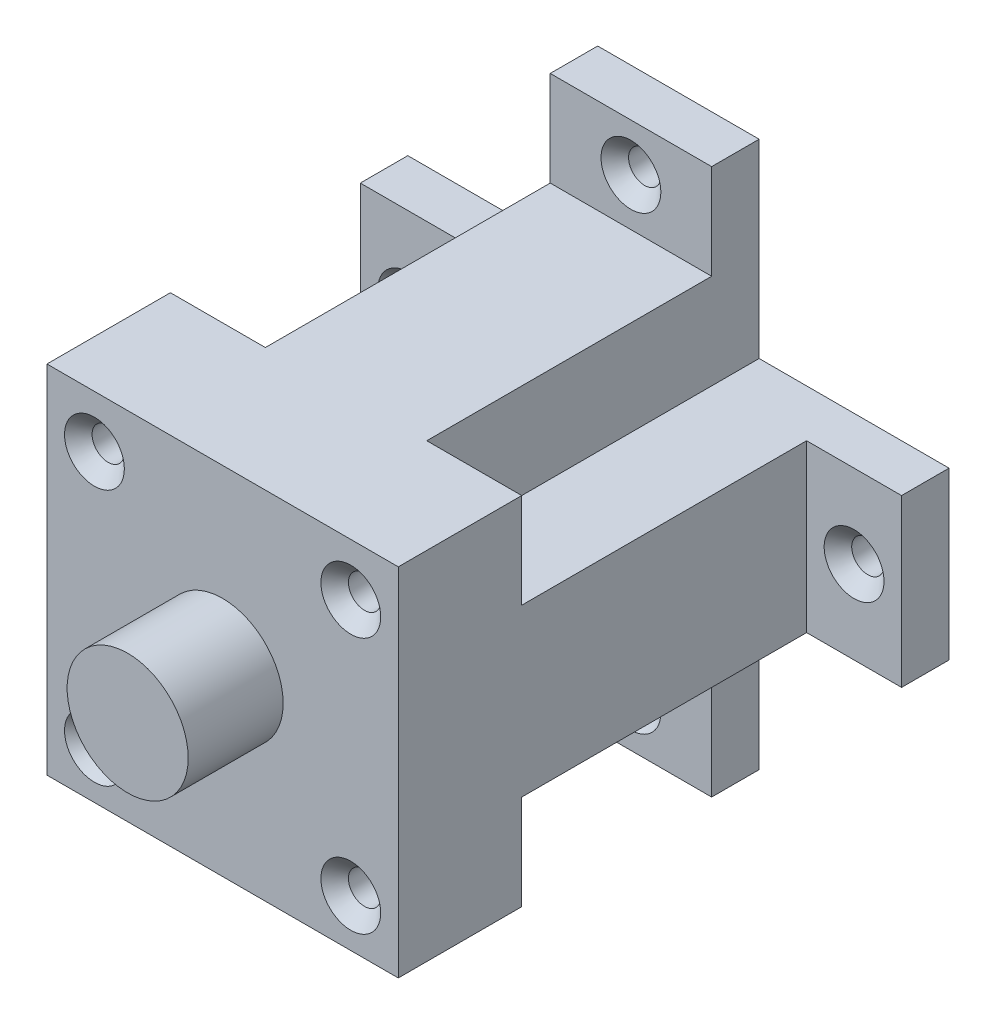
SolidWorks part; units mm, degrees
ref_plane "Plan de face" through (0, 0, 0) normal (0, 0, 1) x (1, 0, 0)
ref_plane "Plan de dessus" through (0, 0, 0) normal (0, 1, 0) x (1, 0, 0)
ref_plane "Plan de droite" through (0, 0, 0) normal (1, 0, 0) x (0, 0, -1)
sketch "Esquisse1" plane through (0, 0, 0) normal (0, 0, 1) x (1, 0, 0)
  line L2 (0, 0) -> (37, 0)
  line L3 (0, 0) -> (0, 37.5)
  line L4 (0, 37.5) -> (37, 37.5)
  line L5 (37, 0) -> (37, 37.5)
  dimension "D1" = 37.5
  dimension "D2" = 37
extrude "Boss.-Extru.1" add sketch "Esquisse1" along normal blind 48
sketch "Esquisse2" plane through (0, 0, 48) normal (0, 0, 1) x (1, 0, 0)
  line L0 (37, 0) -> (37, 37.5) construction
  line L4 (37, 37.5) -> (0, 37.5) construction
  circle A0 centre (18.5, 19) radius 6.375
  dimension "D3" = 12.75
  dimension "D1" = 18.5
  dimension "D2" = 18.5
extrude "Boss.-Extru.2" add sketch "Esquisse2" along normal blind 10
sketch "Esquisse3" plane through (0, 0, 48) normal (0, 0, 1) x (1, 0, 0)
  line L0 (37, 37.5) -> (0, 37.5) construction
  line L1 (0, 37.5) -> (0, 0) construction
  line L2 (37, 0) -> (37, 37.5) construction
  circle A0 centre (5, 32) radius 1.5
  circle A1 centre (32, 32) radius 1.5
  circle A2 centre (32, 5) radius 1.5
  circle A3 centre (5, 5) radius 1.5
  dimension "D3" = 3
  dimension "D5" = 3
  dimension "D9" = 3
  dimension "D11" = 3
  dimension "D1" = 5.5
  dimension "D2" = 5.5
  dimension "5" = 5
  dimension "D4" = 5
  dimension "D6" = 5
  dimension "D7" = 5
  dimension "D8" = 27
  dimension "D10" = 27
hole_wizard "Fraisage pour vis à tête fraisée bombée M31" positions "Esquisse4" profile "Esquisse5" countersink size "M3" standard "ISO"
sketch "Esquisse4" plane through (0, 0, 48) normal (0, 0, 1) x (1, 0, 0)
  point P0 (5, 32)
  point P3 (32, 32)
  point P6 (32, 5)
  point P9 (5, 5)
sketch "Esquisse5" plane through (5, 32, 48) normal (1, 0, 0) x (0, -1, 0)
  line L0 (0, 0) -> (0, 49.0215)
  line L1 (0, 49.0215) -> (1.7, 48)
  line L2 (1.7, 48) -> (1.7, 1.45)
  line L3 (1.7, 1.45) -> (3.15, 0)
  line L5 (3.15, 0) -> (0, 0)
  line L6 (-1.7, 1.45) -> (-3.15, 0) construction
  line L10 (0, 49.0215) -> (-1.7, 48) construction
  line L11 (0, -6.35) -> (0, 107.95) construction
  dimension "Diamètre du perçage" = 3.4
  dimension "Profondeur du perçage" = 48
  dimension "Diamètre du fraisage entrant" = 6.3
  dimension "Angle du fraisage entrant" = 90
  dimension "Angle de pointe" = 118
sketch "Esquisse6" plane through (0, 0, 0) normal (0, -1, 0) x (1, 0, 0)
  line L1 (0, 0) -> (10, 0)
  line L2 (0, 0) -> (0, 5)
  line L3 (0, 5) -> (10, 5)
  line L4 (10, 0) -> (10, 5)
  line L5 (37, 0) -> (27, 0)
  line L6 (37, 0) -> (37, 5)
  line L7 (37, 5) -> (27, 5)
  line L8 (27, 0) -> (27, 5)
  dimension "D1" = 10
  dimension "D2" = 5
  dimension "D3" = 10
  dimension "D4" = 5
extrude "Boss.-Extru.3" [suppressed] add sketch "Esquisse6" along normal blind 10
sketch "Esquisse7" plane through (0, 37.5, 0) normal (0, 1, 0) x (1, 0, 0)
  line L1 (0, 0) -> (10, 0)
  line L2 (0, 0) -> (0, -5)
  line L3 (0, -5) -> (10, -5)
  line L4 (10, 0) -> (10, -5)
  line L5 (37, 0) -> (27, 0)
  line L6 (37, 0) -> (37, -5)
  line L7 (37, -5) -> (27, -5)
  line L8 (27, 0) -> (27, -5)
  dimension "D1" = 5
  dimension "D2" = 5
  dimension "D3" = 10
  dimension "D4" = 10
extrude "Boss.-Extru.4" [suppressed] add sketch "Esquisse7" along normal blind 10
sketch "Esquisse8" [suppressed] plane through (0, 0, 5) normal (0, 0, 1) x (1, 0, 0)
  line L0 (37, -10) -> (27, -10) construction
  line L1 (37, -10) -> (37, 0) construction
  circle A0 centre (32, -5) radius 2.6226
  circle A1 centre (4.4036, -5.1811) radius 2.9344
  circle A2 centre (4.4036, 42.3532) radius 2.5459
  circle A3 centre (32.4325, 42.3532) radius 2.5419
  dimension "D1" = 5
  dimension "5" = 5
sketch "Esquisse10" plane through (0, 0, 0) normal (0, 0, -1) x (-1, 0, 0)
  line L1 (-37, 0) -> (-27, 0)
  line L2 (-37, 0) -> (-37, 10)
  line L3 (-37, 10) -> (-27, 10)
  line L4 (-27, 0) -> (-27, 10)
  line L5 (-37, 37.5) -> (-27, 37.5)
  line L6 (-37, 37.5) -> (-37, 27.5)
  line L7 (-37, 27.5) -> (-27, 27.5)
  line L8 (-27, 37.5) -> (-27, 27.5)
  line L9 (0, 37.5) -> (-10, 37.5)
  line L10 (0, 37.5) -> (0, 27.5)
  line L11 (0, 27.5) -> (-10, 27.5)
  line L12 (-10, 37.5) -> (-10, 27.5)
  line L13 (0, 0) -> (-10, 0)
  line L14 (0, 0) -> (0, 10)
  line L15 (0, 10) -> (-10, 10)
  line L16 (-10, 0) -> (-10, 10)
  dimension "D1" = 10
  dimension "D2" = 10
  dimension "D3" = 10
  dimension "D4" = 10
  dimension "D5" = 10
  dimension "D6" = 10
  dimension "10" = 10
  dimension "D7" = 10
extrude "Enlèv. mat.-Extru.1" cut sketch "Esquisse10" against normal blind 35
sketch "Esquisse11" plane through (0, 0, 0) normal (0, 0, -1) x (-1, 0, 0)
  line L0 (0, 37.5) -> (-10, 37.5) construction
  line L1 (-27, 37.5) -> (-10, 37.5)
  line L2 (-27, 37.5) -> (-27, 47.5)
  line L3 (-27, 47.5) -> (-10, 47.5)
  line L4 (-10, 37.5) -> (-10, 47.5)
  line L5 (-27, 37.5) -> (-10, 37.5) construction
  line L6 (-10, 37.5) -> (-10, 27.5) construction
  line L7 (-10, 37.5) -> (-10, 27.5) construction
  line L8 (-37, 10) -> (-37, 27.5) construction
  line L9 (-37, 27.5) -> (-47, 27.5)
  line L10 (-37, 27.5) -> (-37, 10)
  line L11 (-37, 10) -> (-47, 10)
  line L12 (-47, 27.5) -> (-47, 10)
  line L13 (0, 27.5) -> (10, 27.5)
  line L14 (0, 27.5) -> (0, 10)
  line L15 (0, 10) -> (10, 10)
  line L16 (10, 27.5) -> (10, 10)
  line L17 (-27, 0) -> (-10, 0)
  line L18 (-27, 0) -> (-27, -10)
  line L19 (-27, -10) -> (-10, -10)
  line L20 (-10, 0) -> (-10, -10)
  line L21 (-37, 10) -> (-37, 0) construction
  line L22 (-27, 10) -> (-37, 10) construction
  point P28 (0, 0)
  point P29 (-37, 10)
  point P32 (0, 0)
  point P33 (-10, 0)
  point P35 (0, 0)
  point P36 (0, 10)
  point P38 (-37, 10)
  point P41 (0, 0)
  point P42 (-37, 27.5)
  point P43 (-37, 9.9912)
  point P44 (-37, 10)
  dimension "D1" = 10
  dimension "D2" = 10
  dimension "D3" = 10
  dimension "10" = 10
extrude "Boss.-Extru.5" add sketch "Esquisse11" against normal blind 5
sketch "Esquisse12" plane through (0, 0, 5) normal (0, 0, 1) x (1, 0, 0)
  line L0 (-10, 18.75) -> (0, 18.75) construction
  line L1 (-10, 10) -> (-10, 27.5) construction
  line L2 (0, 27.5) -> (0, 10) construction
  line L3 (18.5, 47.5) -> (18.5, 37.5) construction
  line L4 (10, 47.5) -> (27, 47.5) construction
  line L5 (37, 37.5) -> (0, 37.5) construction
  line L6 (37, 18.75) -> (47, 18.75) construction
  line L7 (37, 10) -> (37, 27.5) construction
  line L8 (47, 27.5) -> (47, 10) construction
  line L9 (18.5, -10) -> (18.5, 0) construction
  line L10 (27, -10) -> (10, -10) construction
  line L11 (10, 0) -> (27, 0) construction
  circle A0 centre (-5, 18.75) radius 1.5
  circle A1 centre (18.5, 42.5) radius 1.5
  circle A2 centre (42, 18.75) radius 1.5
  circle A3 centre (18.5, -5) radius 1.5
  dimension "D1" = 3
  dimension "D2" = 3
  dimension "D3" = 3
  dimension "3" = 3
hole_wizard "Fraisage pour vis à tête fraisée bombée M32" positions "Esquisse13" profile "Esquisse14" countersink size "M3" standard "ISO"
sketch "Esquisse13" plane through (0, 0, 5) normal (0, 0, 1) x (1, 0, 0)
  line L0 (18.5, 47.5) -> (18.5, 37.5) construction
  point P0 (18.5, 42.5)
  point P4 (42, 18.75)
  point P7 (18.5, -5)
  point P10 (-5, 18.75)
sketch "Esquisse14" plane through (18.5, 42.5, 5) normal (1, 0, 0) x (0, -1, 0)
  line L0 (0, 0) -> (0, 6.0215)
  line L1 (0, 6.0215) -> (1.7, 5)
  line L2 (1.7, 5) -> (1.7, 1.45)
  line L3 (1.7, 1.45) -> (3.15, 0)
  line L5 (3.15, 0) -> (0, 0)
  line L6 (-1.7, 1.45) -> (-3.15, 0) construction
  line L10 (0, 6.0215) -> (-1.7, 5) construction
  line L11 (0, -6.35) -> (0, 107.95) construction
  dimension "Diamètre du perçage" = 3.4
  dimension "Profondeur du perçage" = 5
  dimension "Diamètre du fraisage entrant" = 6.3
  dimension "Angle du fraisage entrant" = 90
  dimension "Angle de pointe" = 118
